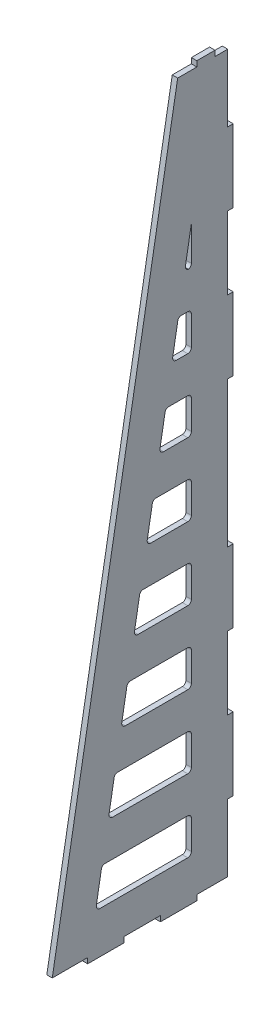
SolidWorks part; units mm, degrees
ref_plane "Front Plane" through (0, 0, 0) normal (0, 0, 1) x (1, 0, 0)
ref_plane "Top Plane" through (0, 0, 0) normal (0, 1, 0) x (1, 0, 0)
ref_plane "Right Plane" through (0, 0, 0) normal (1, 0, 0) x (0, 0, -1)
sketch "Sketch1" plane through (0, 0, 0) normal (1, 0, 0) x (0, 0, -1)
  line L0 (0, 183.8926) -> (0, -216.1074)
  line L3 (-30, 183.8926) -> (-100, -216.1074)
  line L4 (-100, -216.1074) -> (0, -216.1074)
  line L5 (-30, 183.8926) -> (0, 183.8926)
  dimension "D1" = 400
extrude "Boss-Extrude1" add sketch "Sketch1" along normal blind 3
sketch "Sketch2" plane through (3, 0, 0) normal (1, 0, 0) x (0, 0, -1)
  line L2 (-100, -213.1074) -> (0, -213.1074)
  line L3 (-99.475, -213.1074) -> (-80, -213.1074)
  line L5 (-3, -216.1074) -> (-3, 183.8926)
  line L6 (-3, -213.1074) -> (-3, -176.1074)
  line L9 (0, 180.8926) -> (-30, 180.8926)
  line L10 (-3, 180.8926) -> (-10, 180.8926)
  line L14 (-20, -216.1074) -> (-20, -213.1074)
  line L15 (-40, -216.1074) -> (-40, -213.1074)
  line L16 (-60, -216.1074) -> (-60, -213.1074)
  line L17 (-80, -216.1074) -> (-80, -213.1074)
  line L18 (0, 183.8926) -> (-30, 183.8926)
  line L19 (-30, 183.8926) -> (-100, -216.1074)
  line L20 (-100, -216.1074) -> (0, -216.1074)
  line L21 (0, -216.1074) -> (0, 183.8926)
  line L22 (0, 183.8926) -> (-10, 183.8926)
  line L23 (-3, -136.1074) -> (-3, -96.1074)
  line L24 (-100, -216.1074) -> (-80, -216.1074)
  line L25 (0, -216.1074) -> (0, -176.1074)
  line L27 (0, -136.1074) -> (0, -96.1074)
  line L28 (-3, 143.8926) -> (-3, 180.8926)
  line L29 (0, 143.8926) -> (0, 183.8926)
  line L30 (-3, -56.1074) -> (-3, 23.8926)
  line L31 (0, -56.1074) -> (0, 23.8926)
  line L33 (-3, 63.8926) -> (-3, 103.8926)
  line L34 (0, 63.8926) -> (0, 103.8926)
  line L35 (-20, -216.1074) -> (0, -216.1074)
  line L36 (-20, -213.1074) -> (-3, -213.1074)
  line L37 (-60, -216.1074) -> (-40, -216.1074)
  line L38 (-60, -213.1074) -> (-40, -213.1074)
  line L39 (-10, 180.8926) -> (-10, 183.8926)
  line L40 (-20, 180.8926) -> (-20, 183.8926)
  line L41 (-3, -176.1074) -> (0, -176.1074)
  line L42 (-3, -136.1074) -> (0, -136.1074)
  line L43 (-3, -96.1074) -> (0, -96.1074)
  line L44 (-3, -56.1074) -> (0, -56.1074)
  line L45 (-30, 183.8926) -> (-100, -216.1074) construction
  line L46 (-3, 23.8926) -> (0, 23.8926)
  line L47 (-3, 63.8926) -> (0, 63.8926)
  line L48 (-3, 103.8926) -> (0, 103.8926)
  line L49 (-3, 143.8926) -> (0, 143.8926)
  line L50 (-20, 180.8926) -> (-20, 183.8926)
  line L51 (-99.475, -213.1074) -> (-100, -216.1074)
  line L52 (-20, 180.8926) -> (-30.525, 180.8926)
  line L53 (-20, 183.8926) -> (-30, 183.8926)
  line L54 (-30, 183.8926) -> (-30.525, 180.8926)
  line L55 (-99.475, -213.1074) -> (-100, -216.1074)
  line L117 (-30, 180.8926) -> (-30, 183.8926) [skipped]
  line L118 (-100, -216.1074) -> (-100, -213.1074) [skipped]
  line M74 (0, 183.8926) -> (-30, 183.8926)
  line M75 (-30, 183.8926) -> (-100, -216.1074)
  line M76 (-100, -216.1074) -> (0, -216.1074)
  line M77 (0, -216.1074) -> (0, 183.8926)
  dimension "D1" = 3
  dimension "D2" = 3
  dimension "D3" = 3
  dimension "D4" = 0
extrude "Cut-Extrude1" cut sketch "Sketch2" against normal blind 3 contours L43 L23 L42 M77 | L41 L6 L36 L14 M76 M77 | L38 L16 L15 M76 | L17 L3 M76 M75 | L46 L30 L44 M77 | L48 L33 L47 M77 | L28 L49 L39 L10 M77 M74 | L52 L40 M74 M75 region at (3, -214.614, 89.8693) region at (3, 181.8926, 30.175) region at (3, -214.6074, 50) region at (3, 182.3926, 25) region at (3, -214.6074, 11.5) region at (3, 182.3926, 6.5) region at (3, -194.6074, 1.5) region at (3, -214.6074, 1.5) region at (3, 182.3926, 1.5) region at (3, 162.3926, 1.5) region at (3, -116.1074, 1.5) region at (3, 83.8926, 1.5) region at (3, -16.1074, 1.5)
sketch "Sketch3" plane through (3, 0, 0) normal (1, 0, 0) x (0, 0, -1)
  line L0 (-68.6711, -153.1074) -> (-65.1711, -133.1074)
  line L1 (-23, -173.1074) -> (-23, -193.1074)
  line L2 (-61.6711, -113.1074) -> (-58.1711, -93.1074)
  line L3 (-23, -133.1074) -> (-23, -153.1074)
  line L4 (-54.6711, -73.1074) -> (-51.1711, -53.1074)
  line L5 (-23, 107.8701) -> (-23, 86.8926)
  line L6 (-23, -193.1074) -> (-75.6711, -193.1074)
  line L7 (-75.6711, -193.1074) -> (-72.1711, -173.1074)
  line L8 (-23, -173.1074) -> (-72.1711, -173.1074)
  line L9 (-23, -153.1074) -> (-68.6711, -153.1074)
  line L10 (-23, -133.1074) -> (-65.1711, -133.1074)
  line L11 (-23, -113.1074) -> (-61.6711, -113.1074)
  line L12 (-23, -93.1074) -> (-58.1711, -93.1074)
  line L13 (-23, -73.1074) -> (-54.6711, -73.1074)
  line L14 (-23, -53.1074) -> (-51.1711, -53.1074)
  line L15 (-23, -33.1074) -> (-47.6711, -33.1074)
  line L16 (-23, -13.1074) -> (-44.1711, -13.1074)
  line L17 (-23, 6.8926) -> (-40.6711, 6.8926)
  line L18 (-23, 26.8926) -> (-37.1711, 26.8926)
  line L19 (-23, 46.8926) -> (-33.6711, 46.8926)
  line L20 (-23, 66.8926) -> (-30.1711, 66.8926)
  line L21 (-23, 86.8926) -> (-26.6711, 86.8926)
  line L23 (-23, -93.1074) -> (-23, -113.1074)
  line L24 (-47.6711, -33.1074) -> (-44.1711, -13.1074)
  line L25 (-23, -53.1074) -> (-23, -73.1074)
  line L26 (-40.6711, 6.8926) -> (-37.1711, 26.8926)
  line L27 (-23, -13.1074) -> (-23, -33.1074)
  line L28 (-33.6711, 46.8926) -> (-30.1711, 66.8926)
  line L29 (-23, 26.8926) -> (-23, 6.8926)
  line L30 (-26.6711, 86.8926) -> (-23, 107.8701)
  line L31 (-23, 66.8926) -> (-23, 46.8926)
  line L32 (-23, 106.8926) -> (-23.1711, 106.8926) [skipped]
  dimension "D1" = 16
extrude "Cut-Extrude2" cut sketch "Sketch3" against normal blind 3
fillet "Fillet1" radius 2 30 edges at (1.5, 86.8926, 26.6711) (1.5, 86.8926, 23) (1.5, 66.8926, 23) (1.5, 66.8926, 30.1711) (1.5, 46.8926, 23) (1.5, 46.8926, 33.6711) (1.5, 26.8926, 23) (1.5, 26.8926, 37.1711) (1.5, 6.8926, 40.6711) (1.5, 6.8926, 23) (1.5, -33.1074, 23) (1.5, -13.1074, 44.1711) (1.5, -13.1074, 23) (1.5, -93.1074, 23) (1.5, -73.1074, 23) (1.5, -53.1074, 23) (1.5, -53.1074, 51.1711) (1.5, -93.1074, 58.1711) (1.5, -133.1074, 65.1711) (1.5, -133.1074, 23) (1.5, -33.1074, 47.6711) (1.5, -73.1074, 54.6711) (1.5, -113.1074, 61.6711) (1.5, -113.1074, 23) (1.5, -153.1074, 23) (1.5, -153.1074, 68.6711) (1.5, -193.1074, 75.6711) (1.5, -193.1074, 23) (1.5, -173.1074, 23) (1.5, -173.1074, 72.1711)
